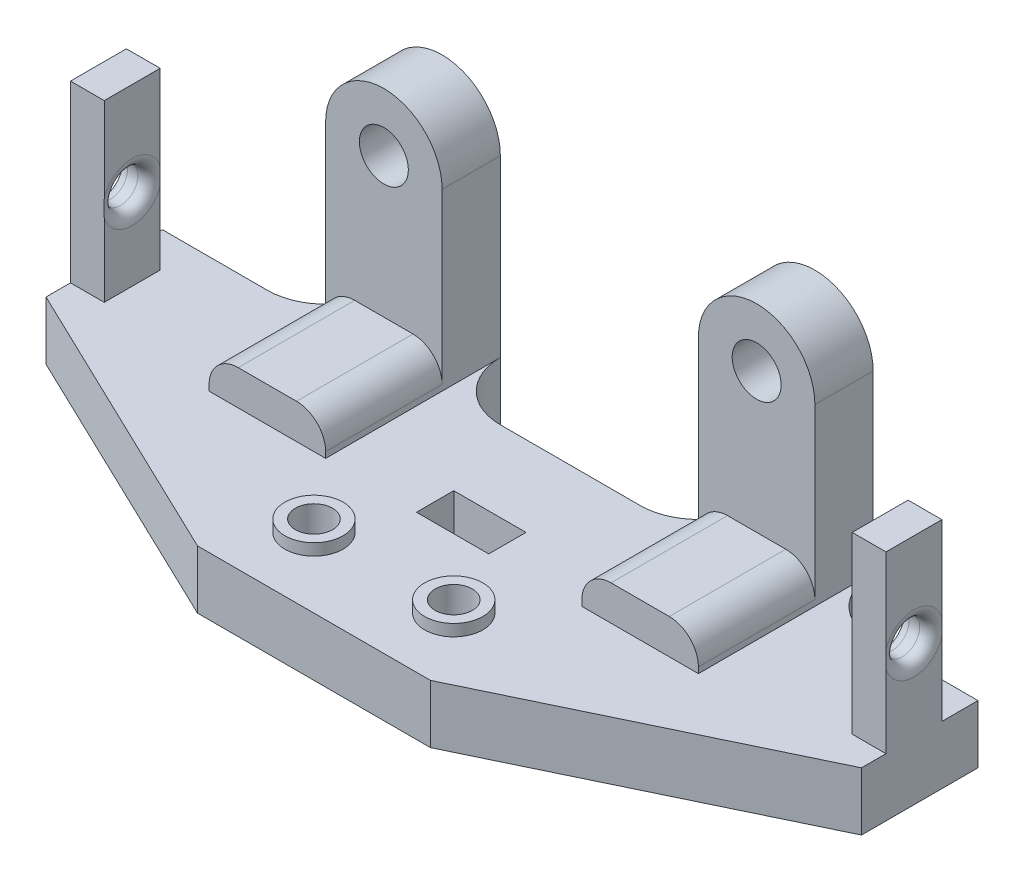
SolidWorks part; units mm, degrees
ref_plane "Front Plane" through (0, 0, 0) normal (0, 0, 1) x (1, 0, 0)
ref_plane "Top Plane" through (0, 0, 0) normal (0, 1, 0) x (1, 0, 0)
ref_plane "Right Plane" through (0, 0, 0) normal (1, 0, 0) x (0, 0, -1)
sketch "Sketch1" plane through (0, 0, 0) normal (0, 1, 0) x (1, 0, 0)
  line L0 (0, 0) -> (20, 0)
  line L1 (10, 0) -> (10, 12) construction
  line L2 (10, 12) -> (-25, 12) construction
  line L3 (0, 0) -> (-25, 12)
  line L4 (-25, 12) -> (-25, 22)
  line L5 (-25, 22) -> (45, 22)
  line L6 (45, 22) -> (45, 12)
  line L7 (45, 12) -> (20, 0)
  dimension "D1" = 35
  dimension "D2" = 20
  dimension "D3" = 12
  dimension "D4" = 70
  dimension "D5" = 10
  dimension "D6" = 10
extrude "Boss-Extrude1" add sketch "Sketch1" along normal blind 5
sketch "Sketch2" plane through (0, 5, 0) normal (0, 1, 0) x (1, 0, 0)
  line L0 (10, 0) -> (10, 22) construction
  line L1 (0, 0) -> (20, 0) construction
  line L2 (45, 22) -> (-25, 22) construction
  circle A0 centre (4, 6) radius 1.6
  circle A1 centre (16, 6) radius 1.6
  dimension "D1" = 3.2
  dimension "D2" = 6
  dimension "D3" = 6
extrude "Cut-Extrude1" cut sketch "Sketch2" against normal blind 3
ref_plane "Plane1" through (0, 0, -6) normal (0, 0, 1) x (1, 0, 0)
sketch "Sketch9" plane through (0, 5, 0) normal (0, 1, 0) x (1, 0, 0)
  line L0 (10, 0) -> (10, 22) construction
  line L1 (0, 0) -> (20, 0) construction
  line L2 (45, 22) -> (-25, 22) construction
  line L3 (10, 11.9) -> (-25, 11.9) construction
  line L4 (-25, 22) -> (-25, 12) construction
  line L5 (-2.75, 6) -> (2.75, 6) construction
  line L7 (6.9, 11.9) -> (13.1, 11.9)
  line L8 (6.9, 11.9) -> (6.9, 15.1)
  line L9 (6.9, 15.1) -> (13.1, 15.1)
  line L10 (13.1, 11.9) -> (13.1, 15.1)
  dimension "D1" = 5.9
  dimension "D2" = 3.1
  dimension "D3" = 3.1
  dimension "D4" = 3.2
sketch "Sketch10" plane through (0, 5, 0) normal (0, 1, 0) x (1, 0, 0)
  line L0 (-25, 22) -> (-25, 12) construction
  line L1 (-25, 18.9) -> (-22.1, 18.9)
  line L2 (-25, 18.9) -> (-25, 14.1)
  line L3 (-25, 14.1) -> (-22.1, 14.1)
  line L4 (-22.1, 18.9) -> (-22.1, 14.1)
  line L5 (45, 22) -> (-25, 22) construction
  line L6 (10, 22) -> (10, 0) construction
  line L7 (0, 0) -> (20, 0) construction
  line L8 (45, 14.1) -> (42.1, 14.1)
  line L9 (42.1, 18.9) -> (42.1, 14.1)
  line L10 (45, 18.9) -> (42.1, 18.9)
  line L11 (45, 18.9) -> (45, 14.1)
  dimension "D1" = 3.1
  dimension "D2" = 4.8
  dimension "D3" = 2.9
extrude "Boss-Extrude2" add sketch "Sketch10" along normal blind 15
extrude "Cut-Extrude4" cut sketch "Sketch9" against normal blind 5
sketch "Sketch11" plane through (-25, 0, 0) normal (-1, 0, 0) x (0, 0, 1)
  circle A0 centre (-16.5, 12) radius 1.5
  dimension "D1" = 3
  dimension "D2" = 7
extrude "Cut-Extrude5" cut sketch "Sketch11" against normal blind 70
fillet "Fillet3" radius 1 1 edges at (-25, 12, -15)
fillet "Fillet4" radius 1 1 edges at (-22.1, 12, -15)
fillet "Fillet6" radius 1 1 edges at (42.1, 12, -18)
fillet "Fillet7" radius 1 1 edges at (45, 12, -15)
sketch "Sketch14" plane through (0, 5, 0) normal (0, 1, 0) x (1, 0, 0)
  circle A0 centre (4, 6) radius 2.5
  circle A1 centre (16, 6) radius 2.5
  circle A2 centre (16, 6) radius 1.6
  circle A3 centre (4, 6) radius 1.6
  dimension "D1" = 5
  dimension "D2" = 5
extrude "Boss-Extrude5" add sketch "Sketch14" along normal blind 1
sketch "Sketch15" plane through (0, 0, -22) normal (0, 0, -1) x (-1, 0, 0)
  line L0 (-45, 0) -> (25, 0) construction
  line L1 (11, 0) -> (1, 0)
  line L2 (11, 0) -> (11, 20)
  line L4 (1, 0) -> (1, 20)
  arc A0 (1, 20) -> (11, 20) centre (6, 20) cw
  circle A1 centre (6, 20) radius 2.1
  point P1 (6, 25)
  point P6 (6, 0)
  dimension "D4" = 4.2
  dimension "D1" = 25
  dimension "D2" = 19
  dimension "D3" = 10
extrude "Boss-Extrude6" add sketch "Sketch15" along normal blind 5
fillet "Fillet8" radius 5 2 edges at (-11, 2.5, -22) (-1, 2.5, -22)
ref_plane "Plane2" through (10, 0, 0) normal (1, 0, 0) x (0, 0, -1)
sketch "Sketch17" plane through (0, 0, -22) normal (0, 0, 1) x (1, 0, 0)
  line L0 (-1, 20) -> (-1, 5) construction
  line L1 (-11, 5) -> (-1, 5)
  line L2 (-11, 5) -> (-11, 5.5)
  line L3 (-8.5, 8) -> (-3.5, 8)
  line L4 (-1, 5) -> (-1, 5.5)
  arc A0 (-3.5, 8) -> (-1, 5.5) centre (-3.5, 5.5) cw
  arc A1 (-11, 5.5) -> (-8.5, 8) centre (-8.5, 5.5) cw
  point P10 (-1, 8)
  point P13 (-11, 8)
  dimension "D2" = 2.5
  dimension "D1" = 12
extrude "Boss-Extrude7" add sketch "Sketch17" along normal blind 10
sketch "Sketch16" plane through (0, 0, -27) normal (0, 0, -1) x (-1, 0, 0)
  line L0 (1, 0) -> (11, 0) construction
  circle A0 centre (6, 4) radius 2.1
  circle A1 centre (6, 20) radius 2.1 construction
  point P4 (0, 0)
  point P7 (6, 0)
  dimension "D1" = 4.2
  dimension "D2" = 16
extrude "Cut-Extrude6" cut sketch "Sketch16" against normal blind 10
mirror "Mirror1" about plane through (10, 0, 0) normal (1, 0, 0) of "Boss-Extrude7", "Fillet8", "Boss-Extrude6", "Cut-Extrude6"
